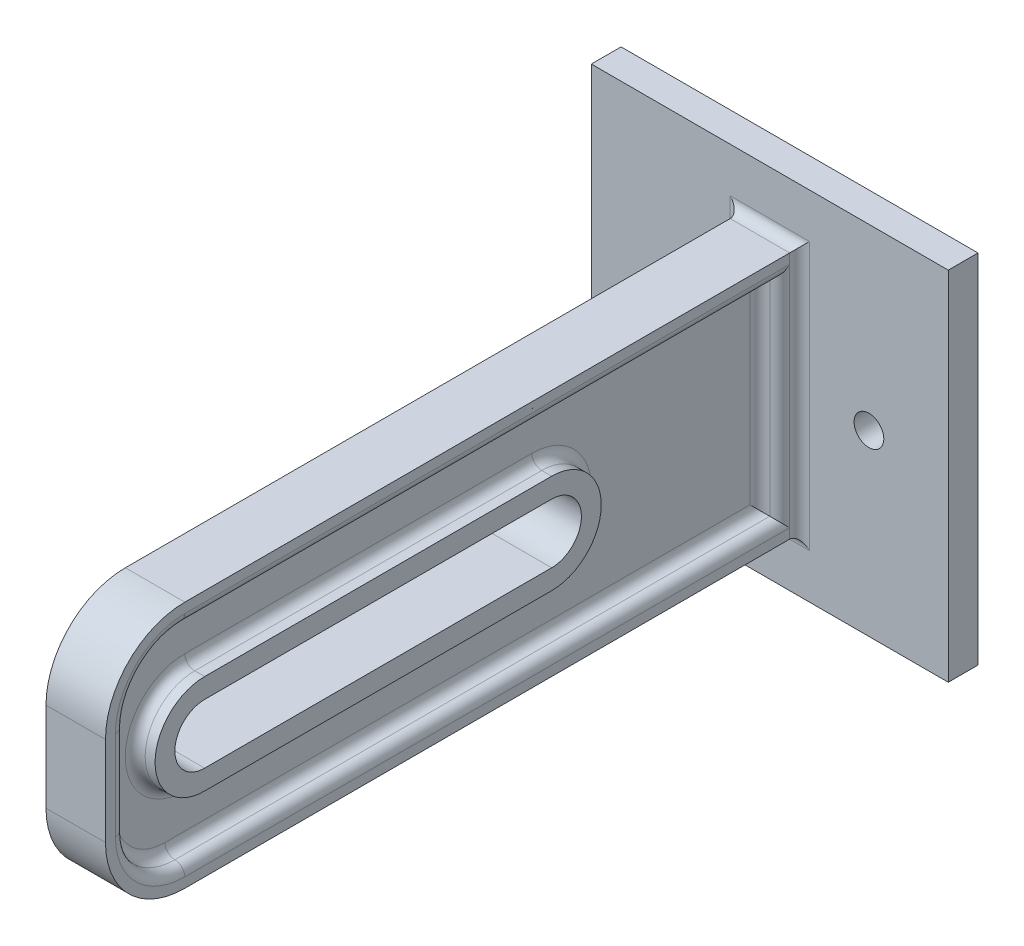
SolidWorks part; units mm, degrees
ref_plane "Front Plane" through (0, 0, 0) normal (0, 0, 1) x (1, 0, 0)
ref_plane "Top Plane" through (0, 0, 0) normal (0, 1, 0) x (1, 0, 0)
ref_plane "Right Plane" through (0, 0, 0) normal (1, 0, 0) x (0, 0, -1)
sketch "Sketch1" plane through (0, 0, 0) normal (0, 0, 1) x (1, 0, 0)
  line L1 (-18, -18) -> (18, -18)
  line L2 (-18, -18) -> (-18, 18)
  line L3 (-18, 18) -> (18, 18)
  line L4 (18, -18) -> (18, 18)
  line L5 (-18, -18) -> (18, 18) construction
  line L6 (-18, 18) -> (18, -18) construction
  point P0 (0, 0)
  dimension "D1" = 36
  dimension "D2" = 36
extrude "Boss-Extrude1" add sketch "Sketch1" along normal mid plane 3
sketch "Sketch2" plane through (0, 0, 1.5) normal (0, 0, 1) x (1, 0, 0)
  line L0 (-10, 0) -> (10, 0) construction
  circle A0 centre (-10, 0) radius 1.5
  circle A1 centre (10, 0) radius 1.5
  point P4 (0, 0)
  dimension "D1" = 3
  dimension "D2" = 20
extrude "Cut-Extrude1" cut sketch "Sketch2" against normal through all
sketch "Sketch3" plane through (0, 0, 1.5) normal (0, 0, 1) x (1, 0, 0)
  line L1 (-3, 12.5) -> (3, 12.5)
  line L2 (-3, 12.5) -> (-3, -12.5)
  line L3 (-3, -12.5) -> (3, -12.5)
  line L4 (3, 12.5) -> (3, -12.5)
  line L5 (-3, 12.5) -> (3, -12.5) construction
  line L6 (-3, -12.5) -> (3, 12.5) construction
  point P0 (0, 0)
  dimension "D1" = 6
  dimension "D2" = 25
extrude "Boss-Extrude2" add sketch "Sketch3" along normal blind 70
sketch "Sketch4" plane through (3, 0, 0) normal (1, 0, 0) x (0, 0, -1)
  line L0 (-61.5, 0) -> (-26.5, 0) construction
  line L1 (-61.5, 3) -> (-26.5, 3)
  line L2 (-61.5, -3) -> (-26.5, -3)
  line L3 (-71.5, -12.5) -> (-71.5, 12.5) construction
  arc A0 (-61.5, 3) -> (-61.5, -3) centre (-61.5, 0) ccw
  arc A1 (-26.5, -3) -> (-26.5, 3) centre (-26.5, 0) ccw
  point P3 (-44, 0)
  dimension "D2" = 35
  dimension "D3" = 3
  dimension "D1" = 10
extrude "Cut-Extrude2" cut sketch "Sketch4" against normal through all
fillet "Fillet1" radius 8 2 edges at (0, 12.5, 71.5) (0, -12.5, 71.5)
sketch "Sketch5" plane through (3, 0, 0) normal (1, 0, 0) x (0, 0, -1)
  line L82 (-3.5, -10.5) -> (-3.5, 10.5)
  line L83 (-3.5, 10.5) -> (-63.5, 10.5)
  line L84 (-69.5, 4.5) -> (-69.5, -4.5)
  line L85 (-63.5, -10.5) -> (-3.5, -10.5)
  line L86 (-3.5, -10.5) -> (-3.5, 10.5)
  line L87 (-3.5, 10.5) -> (-63.5, 10.5)
  line L88 (-69.5, 4.5) -> (-69.5, -4.5)
  line L89 (-63.5, -10.5) -> (-3.5, -10.5)
  line L94 (-26.5, 5) -> (-61.5, 5)
  line L95 (-61.5, -5) -> (-26.5, -5)
  line L96 (-26.5, 5) -> (-61.5, 5)
  line L97 (-61.5, -5) -> (-26.5, -5)
  arc A60 (-63.5, 10.5) -> (-69.5, 4.5) centre (-63.5, 4.5) ccw
  arc A61 (-69.5, -4.5) -> (-63.5, -10.5) centre (-63.5, -4.5) ccw
  arc A62 (-63.5, 10.5) -> (-69.5, 4.5) centre (-63.5, 4.5) ccw
  arc A63 (-69.5, -4.5) -> (-63.5, -10.5) centre (-63.5, -4.5) ccw
  arc A68 (-26.5, -5) -> (-26.5, 5) centre (-26.5, 0) ccw
  arc A69 (-61.5, 5) -> (-61.5, -5) centre (-61.5, 0) ccw
  arc A70 (-26.5, -5) -> (-26.5, 5) centre (-26.5, 0) ccw
  arc A71 (-61.5, 5) -> (-61.5, -5) centre (-61.5, 0) ccw
  dimension "D1" = 2
  dimension "D2" = 2
extrude "Cut-Extrude3" cut sketch "Sketch5" against normal blind 2
mirror "Mirror1" about plane through (0, 0, 0) normal (1, 0, 0) of "Cut-Extrude3"
fillet "Fillet4" radius 1 36 edges at (-3, -10.5, 33.5) (-3, -8.7426, 67.7426) (-3, 0, 69.5) (-3, 8.7426, 67.7426) (3, 10.5, 33.5) (3, 8.7426, 67.7426) (3, 0, 69.5) (3, -8.7426, 67.7426) (-1, 10.5, 33.5) (-1, 8.7426, 67.7426) (-1, 0, 69.5) (-1, -8.7426, 67.7426) (-1, -5, 44) (-1, 0, 66.5) (-1, 5, 44) (1, 10.5, 33.5) (1, 8.7426, 67.7426) (1, 0, 69.5) (1, -8.7426, 67.7426) (1, 0, 21.5) (1, -5, 44) (1, 0, 66.5) (0, 12.5, 1.5) (0, -12.5, 1.5) (-3, 0, 1.5) (3, 0, 1.5) (-3, 10.5, 33.5) (-3, 0, 3.5) (3, 0, 3.5) (3, -10.5, 33.5) (-1, 0, 3.5) (-1, -10.5, 33.5) (-1, 0, 21.5) (1, 0, 3.5) (1, -10.5, 33.5) (1, 5, 44)
